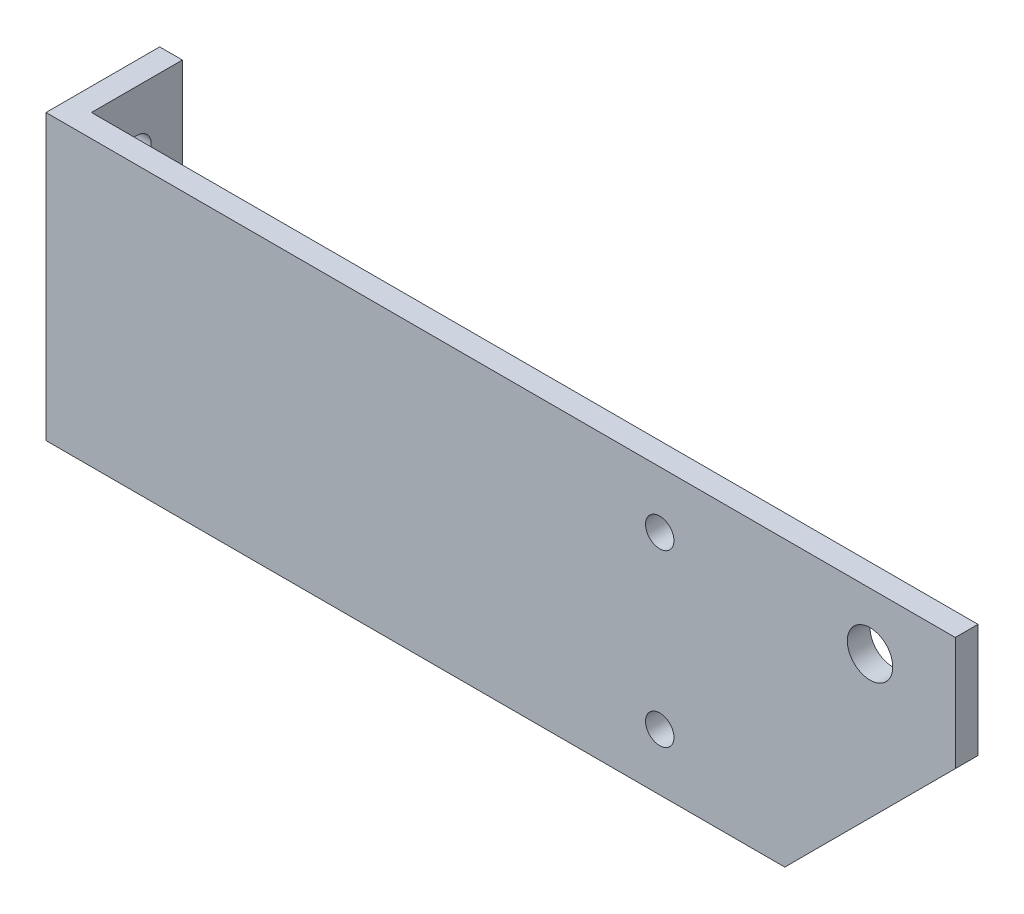
SolidWorks part; units mm, degrees
ref_plane "Спереди" through (0, 0, 0) normal (0, 0, 1) x (1, 0, 0)
ref_plane "Сверху" through (0, 0, 0) normal (0, 1, 0) x (1, 0, 0)
ref_plane "Справа" through (0, 0, 0) normal (1, 0, 0) x (0, 0, -1)
sketch "Эскиз1" plane through (0, 0, 0) normal (0, 1, 0) x (1, 0, 0)
  line L1 (0, 0) -> (160, 0)
  line L2 (0, 0) -> (0, 4)
  line L3 (4, 4) -> (160, 4)
  line L4 (160, 0) -> (160, 4)
  line L6 (0, 4) -> (0, 20)
  line L7 (0, 20) -> (4, 20)
  line L8 (4, 4) -> (4, 20)
  dimension "D1" = 160
  dimension "D2" = 4
  dimension "D3" = 20
  dimension "D4" = 4
extrude "Бобышка-Вытянуть1" add sketch "Эскиз1" along normal blind 50
sketch "Эскиз2" plane through (0, 0, 0) normal (-1, 0, 0) x (0, 0, 1)
  line L0 (-12, 44.9311) -> (-12, 11.555) construction
  line L2 (-20, 0) -> (0, 0) construction
  line L3 (0, 50) -> (0, 0) construction
  circle A0 centre (-12, 40) radius 2.5
  circle A1 centre (-12, 10) radius 2.5
  dimension "D2" = 5
  dimension "D3" = 5
  dimension "D1" = 12
  dimension "D4" = 30
  dimension "D5" = 10
extrude "Вырез-Вытянуть1" cut sketch "Эскиз2" against normal blind 10
sketch "Эскиз3" plane through (0, 0, 0) normal (0, 0, 1) x (1, 0, 0)
  line L0 (108, 46.6766) -> (108, 6.7064) construction
  line L1 (160, 50) -> (160, 0) construction
  line L2 (0, 0) -> (160, 0) construction
  line L4 (0, 50) -> (0, 0) construction
  circle A0 centre (108, 40) radius 2.5
  circle A1 centre (108, 10) radius 2.5
  circle A2 centre (145, 40) radius 4
  dimension "D2" = 5
  dimension "D3" = 5
  dimension "D6" = 8
  dimension "D1" = 108
  dimension "D4" = 30
  dimension "D5" = 10
  dimension "D7" = 15
extrude "Вырез-Вытянуть2" cut sketch "Эскиз3" against normal blind 10
sketch "Эскиз4" plane through (0, 0, 0) normal (0, 0, 1) x (1, 0, 0)
  line L0 (160, 30) -> (130, 0)
  line L1 (160, 50) -> (160, 0) construction
  line L2 (0, 0) -> (160, 0) construction
  line L3 (130, 0) -> (160, 0)
  line L4 (160, 0) -> (160, 30)
  dimension "D1" = 30
  dimension "D2" = 30
extrude "Вырез-Вытянуть3" cut sketch "Эскиз4" against normal blind 10
